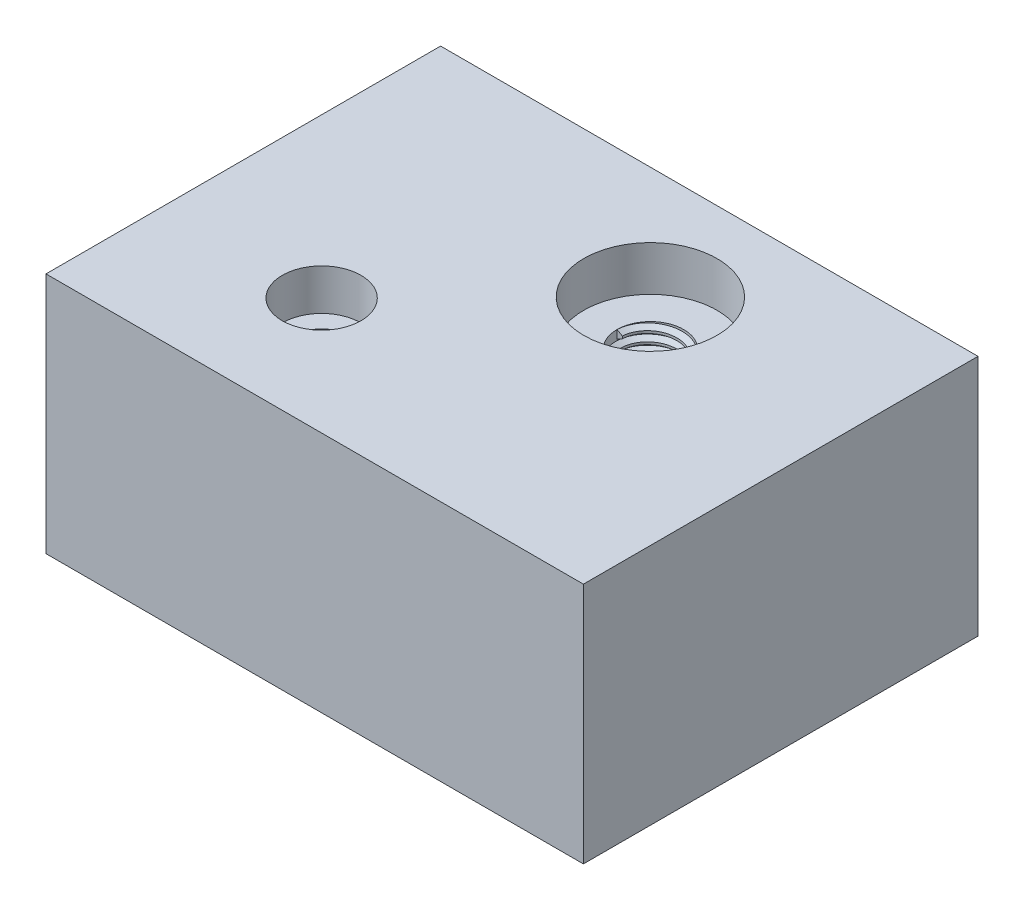
SolidWorks part; units mm, degrees
other "标注1"
sketch "草图7" plane through (7.1985, 20, 18.2995) normal (0.0951, 0.8967, 0.4323) x (0.5387, -0.4115, 0.7352)
other "标注2"
sketch "草图8" plane through (7.1985, 20, 18.2995) normal (0.0951, 0.8967, 0.4323) x (0.5387, -0.4115, 0.7352)
ref_plane "前视基准面" through (0, 0, 0) normal (0, 0, 1) x (1, 0, 0)
ref_plane "上视基准面" through (0, 0, 0) normal (0, 1, 0) x (1, 0, 0)
ref_plane "右视基准面" through (0, 0, 0) normal (1, 0, 0) x (0, 0, -1)
other "Configuration Table"
sketch "草图1" plane through (0, 0, 0) normal (0, 1, 0) x (1, 0, 0)
  line L0 (7.1985, 14.2696) -> (7.1985, -18.2995)
  line L1 (-37.1562, 14.2696) -> (7.1985, 14.2696)
  line L2 (-37.1562, 14.2696) -> (-37.1562, -18.2995)
  line L3 (-37.1562, -18.2995) -> (7.1985, -18.2995)
extrude "凸台-拉伸1" add sketch "草图1" along normal blind 20
hole_wizard "M3 六角凹头螺钉的柱形沉头孔1" positions "3D草图1" profile "草图2" counterbore size "M3" standard "ISO" end condition through all
sketch3d "3D草图1"
  point P0 (-24.0546, 20, 8.6511)
sketch "草图2" plane through (-24.0546, 20, 8.6511) normal (1, 0, 0) x (0, 0, 1)
  line L0 (0, 0) -> (0, 20)
  line L1 (0, 20) -> (1.7, 20)
  line L3 (1.7, 20) -> (1.7, 3.4)
  line L4 (1.7, 3.4) -> (3.25, 3.4)
  line L5 (3.25, 3.4) -> (3.25, 0)
  line L7 (3.25, 0) -> (0, 0)
  line L11 (0, -6.35) -> (0, 107.95) construction
  dimension "通孔孔直径" = 3.4
  dimension "通孔孔深度" = 20
  dimension "柱形沉头孔直径" = 6.5
  dimension "柱形沉头孔深度" = 3.4
thread "螺纹线1" pitch 0.5 method extrude profile "螺纹线轮廓1" start angle 0, offset 0, length 10, pitch 0.5, diameter 3.4
ref_plane "基准面1" through (-22.3546, 0, 8.6511) normal (0, 0, 1) x (1, 0, 0)
sketch "螺纹线轮廓1" plane through (-22.3546, 0, 8.6511) normal (0, 0, 1) x (1, 0, 0)
  line L0 (0, 0) -> (0, 0.5) construction
  line L11 (0, 0) -> (0, 0.4375)
  line L12 (0, 0.4375) -> (-0.2706, 0.2812)
  line L13 (-0.2706, 0.2812) -> (-0.2706, 0.1562)
  line L15 (-0.2706, 0.1562) -> (0, 0)
  line L17 (-0.2706, 0.2187) -> (0, 0.2187) construction
  point P2 (0, 0)
  dimension "Pitch" = 0.5
  dimension "Profile_Angle" = 60
  dimension "Profile_Land" = 0.125
  dimension "Profile_Height" = 0.2706
hole_wizard "M5 平盘头螺钉的柱形沉头孔1" positions "3D草图2" profile "草图6" counterbore size "M5" standard "ISO"
sketch3d "3D草图2"
  point P0 (-10.5643, 20, -4.9919)
sketch "草图6" plane through (-10.5643, 20, -4.9919) normal (1, 0, 0) x (0, 0, 1)
  line L0 (0, 0) -> (0, 13.6524)
  line L1 (0, 13.6524) -> (2.75, 12)
  line L2 (2.75, 12) -> (2.75, 3.7)
  line L3 (2.75, 3.7) -> (5.5, 3.7)
  line L4 (5.5, 3.7) -> (5.5, 0)
  line L5 (5.5, 0) -> (0, 0)
  line L10 (0, 13.6524) -> (-2.75, 12) construction
  line L11 (0, -6.35) -> (0, 107.95) construction
  dimension "孔直径" = 5.5
  dimension "孔深度" = 12
  dimension "柱形沉头孔直径" = 11
  dimension "柱形沉头孔深度" = 3.7
  dimension "导头角度" = 118
thread "螺纹线2" pitch 0.8 method extrude profile "螺纹线轮廓2" start angle 0, offset 0, length 8, pitch 0.8, diameter 5.5
ref_plane "基准面2" through (-13.3143, 16.3, -4.9919) normal (0, 0, 1) x (-1, 0, 0)
sketch "螺纹线轮廓2" plane through (-13.3143, 16.3, -4.9919) normal (0, 0, 1) x (-1, 0, 0)
  line L0 (0, 0) -> (0, 0.8) construction
  line L11 (0, 0) -> (0, 0.7)
  line L12 (0, 0.7) -> (-0.433, 0.45)
  line L13 (-0.433, 0.45) -> (-0.433, 0.25)
  line L15 (-0.433, 0.25) -> (0, 0)
  line L17 (-0.433, 0.35) -> (0, 0.35) construction
  point P2 (0, 0)
  dimension "Pitch" = 0.8
  dimension "Profile_Angle" = 60
  dimension "Profile_Land" = 0.2
  dimension "Profile_Height" = 0.433
